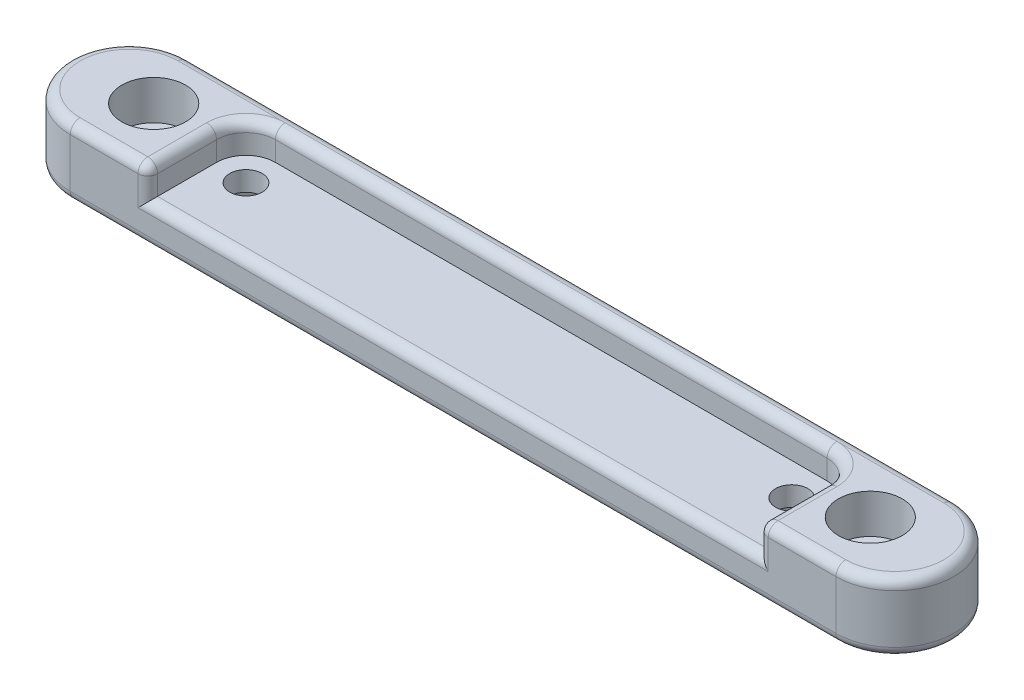
SolidWorks part; units mm, degrees
ref_plane "Plan de face" through (0, 0, 0) normal (0, 0, 1) x (1, 0, 0)
ref_plane "Plan de dessus" through (0, 0, 0) normal (0, 1, 0) x (1, 0, 0)
ref_plane "Plan de droite" through (0, 0, 0) normal (1, 0, 0) x (0, 0, -1)
sketch "Esquisse1" plane through (0, 0, 0) normal (0, 1, 0) x (1, 0, 0)
  line L0 (-27.8, 0) -> (27.8, 0) construction
  line L1 (0, 0) -> (0, 3.3) construction
  line L3 (-31.1, -6.7) -> (-31.1, 3.3)
  line L4 (-31.1, 3.3) -> (31.1, 3.3)
  line L5 (31.1, -6.7) -> (31.1, 3.3)
  line L6 (-31.1, -6.7) -> (31.1, -6.7)
  circle A0 centre (-27.8, 0) radius 1.65
  circle A1 centre (27.8, 0) radius 1.65
  point P4 (0, 0)
  point P7 (0, 0)
  point P12 (-34.6013, -3.296)
  point P15 (-31.1, -6.8958)
  dimension "D1" = 3.3
  dimension "D2" = 55.6
  dimension "D3" = 62.2
  dimension "D4" = 3.3
  dimension "D5" = 10
extrude "Boss.-Extru.1" add sketch "Esquisse1" along normal blind 4
sketch "Esquisse2" plane through (0, 4, 0) normal (0, 1, 0) x (1, 0, 0)
  line L0 (-31.1, -6.7) -> (-31.1, 3.3)
  line L1 (-31.1, 3.3) -> (31.1, 3.3)
  line L2 (31.1, 3.3) -> (31.1, -6.7)
  line L3 (31.1, -6.7) -> (33.5, -6.7)
  line L4 (33.5, -6.7) -> (33.5, 5.3)
  line L5 (33.5, 5.3) -> (-33.5, 5.3)
  line L6 (-33.5, 5.3) -> (-33.5, -6.7)
  line L7 (-33.5, -6.7) -> (-31.1, -6.7)
  dimension "D1" = 67
  dimension "D2" = 2
extrude "Boss.-Extru.2" add sketch "Esquisse2" along normal blind 3 and the other way up to surface (4 mm away) other way up to face at (-27.8, 0, 1.65)
fillet "Congé1" radius 3 2 edges at (31.1, 5.5, -3.3) (-31.1, 5.5, -3.3)
sketch "Esquisse3" plane through (0, 7, 0) normal (0, 1, 0) x (1, 0, 0)
  line L0 (0, 5.3) -> (0, -6.7) construction
  line L1 (33.5, 5.3) -> (-33.5, 5.3) construction
  line L2 (-31.1, -6.7) -> (31.1, -6.7) construction
  line L3 (-39, 5.3) -> (-39, -6.7) construction
  line L4 (-39, 5.3) -> (-33.5, 5.3)
  line L5 (-33.5, 5.3) -> (-33.5, -6.7)
  line L6 (-33.5, -6.7) -> (-39, -6.7)
  line L7 (33.5, 5.3) -> (33.5, -6.7)
  line L8 (39, 5.3) -> (33.5, 5.3)
  line L9 (33.5, -6.7) -> (39, -6.7)
  line L10 (-33.5, -0.7) -> (-36.5, -0.7) construction
  arc A0 (-39, 5.3) -> (-39, -6.7) centre (-39, -0.7) ccw
  arc A1 (39, 5.3) -> (39, -6.7) centre (39, -0.7) cw
  circle A2 centre (-36.5, -0.7) radius 1.65
  circle A3 centre (36.5, -0.7) radius 1.65
  point P21 (-36.5, -0.7)
  dimension "D2" = 3.3
  dimension "D1" = 5.5
  dimension "D3" = 3
extrude "Boss.-Extru.3" add sketch "Esquisse3" against normal up to surface (7 mm away) up to face at (-27.8, 0, 1.65)
sketch "Esquisse5" plane through (0, 0, 0) normal (0, -1, 0) x (1, 0, 0)
  line L6 (-29.4454, 2.85) -> (-26.1546, 2.85)
  line L7 (-26.1546, 2.85) -> (-24.5091, 0)
  line L8 (-24.5091, 0) -> (-26.1546, -2.85)
  line L9 (-26.1546, -2.85) -> (-29.4454, -2.85)
  line L10 (-29.4454, -2.85) -> (-31.0909, 0)
  line L11 (-31.0909, 0) -> (-29.4454, 2.85)
  line L12 (-31.0909, 0) -> (-24.5091, 0) construction
  line L13 (26.1546, 2.85) -> (29.4454, 2.85)
  line L14 (29.4454, 2.85) -> (31.0909, 0)
  line L15 (31.0909, 0) -> (29.4454, -2.85)
  line L16 (29.4454, -2.85) -> (26.1546, -2.85)
  line L17 (26.1546, -2.85) -> (24.5091, 0)
  line L18 (24.5091, 0) -> (26.1546, 2.85)
  line L19 (24.5091, 0) -> (31.0909, 0) construction
  point P0 (-27.8, 0)
  point P1 (27.8, 0)
  point P2 (-27.8, 0)
  point P5 (-27.8, 0)
  point P12 (-27.8, 0)
  point P13 (27.8, 0)
  point P16 (27.8, 0)
  point P21 (27.8, 0)
  point P22 (0, 0)
  point P23 (0, 0)
  point P24 (0, 0)
  dimension "D1" = 120
  dimension "D2" = 120
  dimension "D3" = 5.7
  dimension "D4" = 5.7
extrude "Enlèv. mat.-Extru.1" cut sketch "Esquisse5" against normal blind 2
sketch "Esquisse6" plane through (0, 7, 0) normal (0, 1, 0) x (1, 0, 0)
  circle A0 centre (-36.5, -0.7) radius 3.25
  circle A1 centre (36.5, -0.7) radius 3.25
  dimension "D1" = 6.5
extrude "Enlèv. mat.-Extru.2" cut sketch "Esquisse6" against normal blind 4
fillet "Congé2" radius 1 17 edges at (31.1, 7, 3.2) (30.2213, 7, -2.4213) (0, 7, -3.3) (-30.2213, 7, -2.4213) (-45, 0, 0.7) (0, 0, -5.3) (45, 0, 0.7) (35.05, 7, 6.7) (45, 7, 0.7) (0, 7, -5.3) (-35.05, 7, 6.7) (31.1, 5.5, 6.7) (-31.1, 5.5, 6.7) (-31.1, 7, 3.2) (0, 4, 6.7) (0, 0, 6.7) (-45, 7, 0.7)
